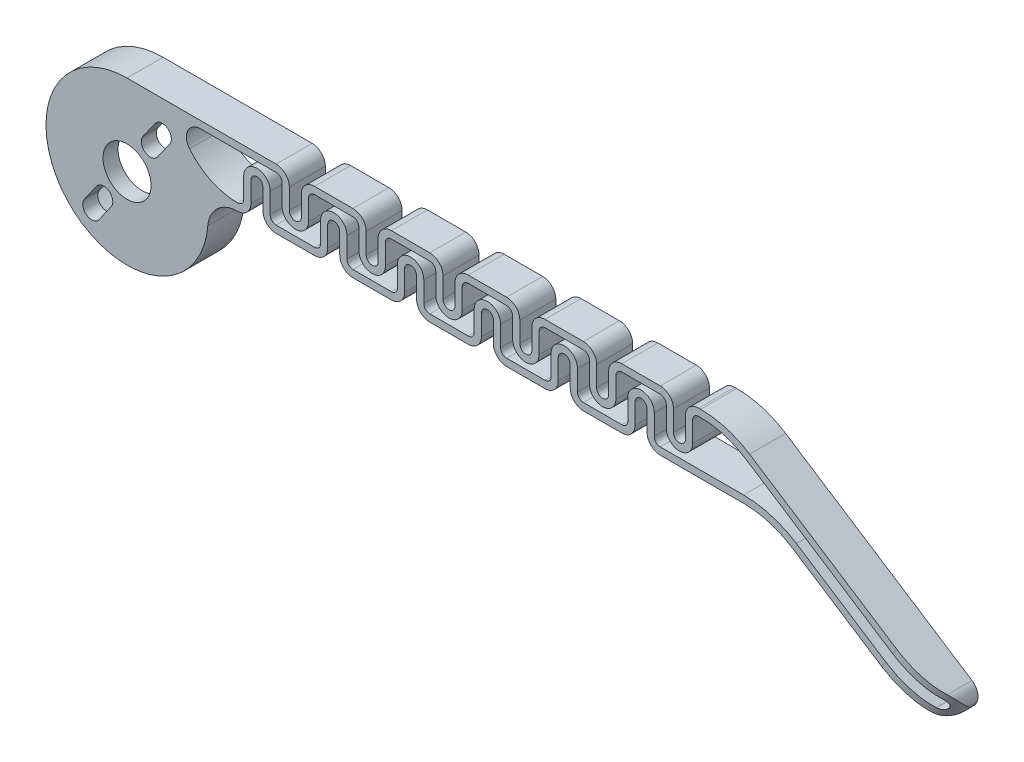
SolidWorks part; units mm, degrees
material "ABS"
ref_plane "Front" through (0, 0, 0) normal (0, 0, 1) x (1, 0, 0)
ref_plane "Top" through (0, 0, 0) normal (0, 1, 0) x (1, 0, 0)
ref_plane "Right" through (0, 0, 0) normal (1, 0, 0) x (0, 0, -1)
sketch "Esquisse1" plane through (0, 0, 0) normal (0, 0, 1) x (1, 0, 0)
  line L2 (0, 13.5) -> (100, 13.5)
  line L3 (13.0384, 3.5) -> (107.1592, 3.5)
  line L4 (100, 13.5) -> (136.618, -10.2233)
  line L5 (136.618, -10.2233) -> (134.1713, -14)
  line L6 (134.1713, -14) -> (107.1592, 3.5)
  arc A0 (0, 13.5) -> (13.0384, 3.5) centre (0, 0) ccw
  circle A1 centre (0, 0) radius 4
  circle A2 centre (0, 0) radius 137.5 construction
  dimension "D1" = 13.5
  dimension "D4" = 8
  dimension "D5" = 137
  dimension "D9" = 275
  dimension "D2" = 10
  dimension "D3" = 4.5
  dimension "D6" = 100
  dimension "D7" = 14
  dimension "D8" = 32.938
extrude "Boss.-Extru.1" add sketch "Esquisse1" along normal mid plane 6
sketch "Esquisse5" plane through (0, 0, 3) normal (0, 0, 1) x (1, 0, 0)
  circle A0 centre (0, 0) radius 12.25
  circle A1 centre (0, 0) radius 4 construction
  dimension "D1" = 24.5
extrude "Enlèv. mat.-Extru.3" cut sketch "Esquisse5" against normal through all from offset 2.5 offset against normal yes
sketch "Esquisse6" plane through (0, 0, 3) normal (0, 0, 1) x (1, 0, 0)
  line L0 (-4.8754, -6.9628) -> (4.8754, 6.9628) construction
  line L1 (5.8792, 8.3963) -> (3.8716, 5.5293) construction
  line L2 (0, -50) -> (0, 50) construction
  line L3 (7.1079, 7.5359) -> (5.1004, 4.6689)
  line L4 (4.6504, 9.2567) -> (2.6429, 6.3896)
  line L5 (-3.8716, -5.5293) -> (-5.8792, -8.3963) construction
  line L6 (-2.6429, -6.3896) -> (-4.6504, -9.2567)
  line L7 (-5.1004, -4.6689) -> (-7.1079, -7.5359)
  circle A0 centre (4.8754, 6.9628) radius 1.5 construction
  circle A1 centre (-4.8754, -6.9628) radius 1.5 construction
  circle A2 centre (0, 0) radius 4 construction
  arc A3 (7.1079, 7.5359) -> (4.6504, 9.2567) centre (5.8792, 8.3963) ccw
  arc A4 (2.6429, 6.3896) -> (5.1004, 4.6689) centre (3.8716, 5.5293) ccw
  arc A5 (-2.6429, -6.3896) -> (-5.1004, -4.6689) centre (-3.8716, -5.5293) ccw
  arc A6 (-7.1079, -7.5359) -> (-4.6504, -9.2567) centre (-5.8792, -8.3963) ccw
  point P4 (0, 0)
  point P11 (4.8754, 6.9628)
  point P16 (-4.8754, -6.9628)
  dimension "D1" = 3
  dimension "D2" = 17
  dimension "D3" = 35
  dimension "D4" = 3.5
extrude "Enlèv. mat.-Extru.4" cut sketch "Esquisse6" against normal through all
fillet "Congé4" radius 5 1 edges at (13.0384, 3.5, 0)
fillet "Congé3" radius 15 2 edges at (107.1592, 3.5, 0) (100, 13.5, 0)
sketch "Esquisse7" plane through (0, 0, 3) normal (0, 0, 1) x (1, 0, 0)
  circle A0 centre (0, 0) radius 13.5
  arc A2 (0, 13.5) -> (13.4556, -1.0946) centre (0, 0) ccw construction
extrude "Boss.-Extru.2" [suppressed] add sketch "Esquisse7" against normal blind 0.2
fillet "Congé5" radius 5 1 edges at (135.3946, -12.1117, 3)
sketch "Esquisse8" plane through (0, 0, -3) normal (0, 0, -1) x (-1, 0, 0)
  line L0 (-22.6391, 9.1) -> (-22.6391, 5.7)
  line L3 (-95.5657, 13.5) -> (0, 13.5) construction
  line L4 (-18.4391, 3.5) -> (-102.7249, 3.5) construction
  line L5 (-24.8391, 3.5) -> (-18.4391, 3.5)
  line L6 (-20.6391, 5.7) -> (-20.6391, 9.1)
  line L7 (-24.8391, 4.7) -> (-24.8391, 12.3) construction
  line L8 (-24.8391, 12.3) -> (-18.4391, 12.3)
  line L9 (-18.4391, 12.3) -> (-18.4391, 4.7)
  line L10 (-19.4391, 5.7) -> (-19.4391, 9.1)
  line L11 (-23.8391, 9.1) -> (-23.8391, 5.7)
  line L12 (-24.8391, 4.7) -> (-31.2391, 4.7)
  line L13 (-31.2391, 4.7) -> (-31.2391, 12.3)
  line L14 (-30.2391, 11.3) -> (-30.2391, 7.9)
  line L15 (-25.8391, 7.9) -> (-25.8391, 11.3)
  line L16 (-31.2391, 13.5) -> (-24.8391, 13.5)
  line L17 (-29.0391, 11.3) -> (-29.0391, 7.9)
  line L18 (-27.0391, 7.9) -> (-27.0391, 11.3)
  arc A2 (-22.6391, 5.7) -> (-24.8391, 3.5) centre (-24.8391, 5.7) cw
  arc A3 (-18.4391, 3.5) -> (-20.6391, 5.7) centre (-18.4391, 5.7) cw
  arc A4 (-20.6391, 9.1) -> (-22.6391, 9.1) centre (-21.6391, 9.1) ccw
  arc A5 (-18.4391, 4.7) -> (-19.4391, 5.7) centre (-18.4391, 5.7) cw
  arc A6 (-19.4391, 9.1) -> (-23.8391, 9.1) centre (-21.6391, 9.1) ccw
  arc A7 (-23.8391, 5.7) -> (-24.8391, 4.7) centre (-24.8391, 5.7) cw
  arc A8 (-31.2391, 12.3) -> (-30.2391, 11.3) centre (-31.2391, 11.3) cw
  arc A9 (-30.2391, 7.9) -> (-25.8391, 7.9) centre (-28.0391, 7.9) ccw
  arc A10 (-25.8391, 11.3) -> (-24.8391, 12.3) centre (-24.8391, 11.3) cw
  arc A11 (-31.2391, 13.5) -> (-29.0391, 11.3) centre (-31.2391, 11.3) cw
  arc A12 (-29.0391, 7.9) -> (-27.0391, 7.9) centre (-28.0391, 7.9) ccw
  arc A13 (-27.0391, 11.3) -> (-24.8391, 13.5) centre (-24.8391, 11.3) cw
  dimension "D1" = 2
  dimension "D2" = 1.2
  dimension "D5" = 1
  dimension "D3" = 1.2
  dimension "D4" = 6.4
extrude "Enlèv. mat.-Extru.5" cut sketch "Esquisse8" against normal through all and the other way through all
pattern_linear "Répétition linéaire1" count 6 spacing 12.8 along (1, 0, 0) of "Enlèv. mat.-Extru.5"
sketch "Esquisse9" plane through (0, 0, -3) normal (0, 0, -1) x (-1, 0, 0)
  line L0 (-18.4391, 12.3) -> (-18.4391, 4.7)
  line L1 (-12.2193, 12.3) -> (-18.4391, 12.3)
  line L2 (-12.2193, 9.9758) -> (-10.4188, 8.5059) construction
  line L13 (-134.9584, -10.578) -> (-133.8166, -12.3404)
  line L14 (-133.8166, -12.3404) -> (-111.5332, 2.0961)
  line L15 (-103.0691, 10.0818) -> (-134.9584, -10.578)
  line L16 (-134.4147, -11.4172) -> (-134.3603, -11.5012)
  line L17 (-132.9774, -11.7967) -> (-111.5332, 2.0961)
  line L18 (-103.0691, 10.0818) -> (-134.1192, -10.0342)
  line L19 (-102.7249, 4.7) -> (-95.2391, 4.7)
  line L20 (-95.2391, 4.7) -> (-95.2391, 12.2961)
  line L22 (-95.2391, 4.7) -> (-95.2391, 12.3) construction
  line L23 (-88.8391, 4.7) -> (-95.2391, 4.7) construction
  arc A1 (-18.4391, 4.7) -> (-10.4188, 8.5059) centre (-18.4391, 15.0536) ccw
  arc A2 (-10.4188, 8.5059) -> (-12.2193, 12.3) centre (-12.2193, 9.9758) ccw
  circle A3 centre (0, 0) radius 12.25 construction
  arc A9 (-134.3603, -11.5012) -> (-132.9774, -11.7967) centre (-133.5211, -10.9574) ccw
  arc A10 (-134.4147, -11.4172) -> (-134.1192, -10.0342) centre (-133.5754, -10.8735) cw
  arc A11 (-102.7249, 4.7) -> (-111.5332, 2.0961) centre (-102.7249, -11.5) ccw
  arc A12 (-95.5657, 12.3) -> (-103.0691, 10.0818) centre (-95.5657, -1.5) ccw
  arc A13 (-102.7249, 4.7) -> (-111.5332, 2.0961) centre (-102.7249, -11.5) ccw
  arc A14 (-95.2391, 12.2961) -> (-103.0691, 10.0818) centre (-95.5657, -1.5) ccw
  dimension "D1" = 1.2
  dimension "D2" = 1.2
  dimension "D3" = 1
extrude "Enlèv. mat.-Extru.6" cut sketch "Esquisse9" against normal through all
fillet "Congé6" radius 2.2 2 edges
